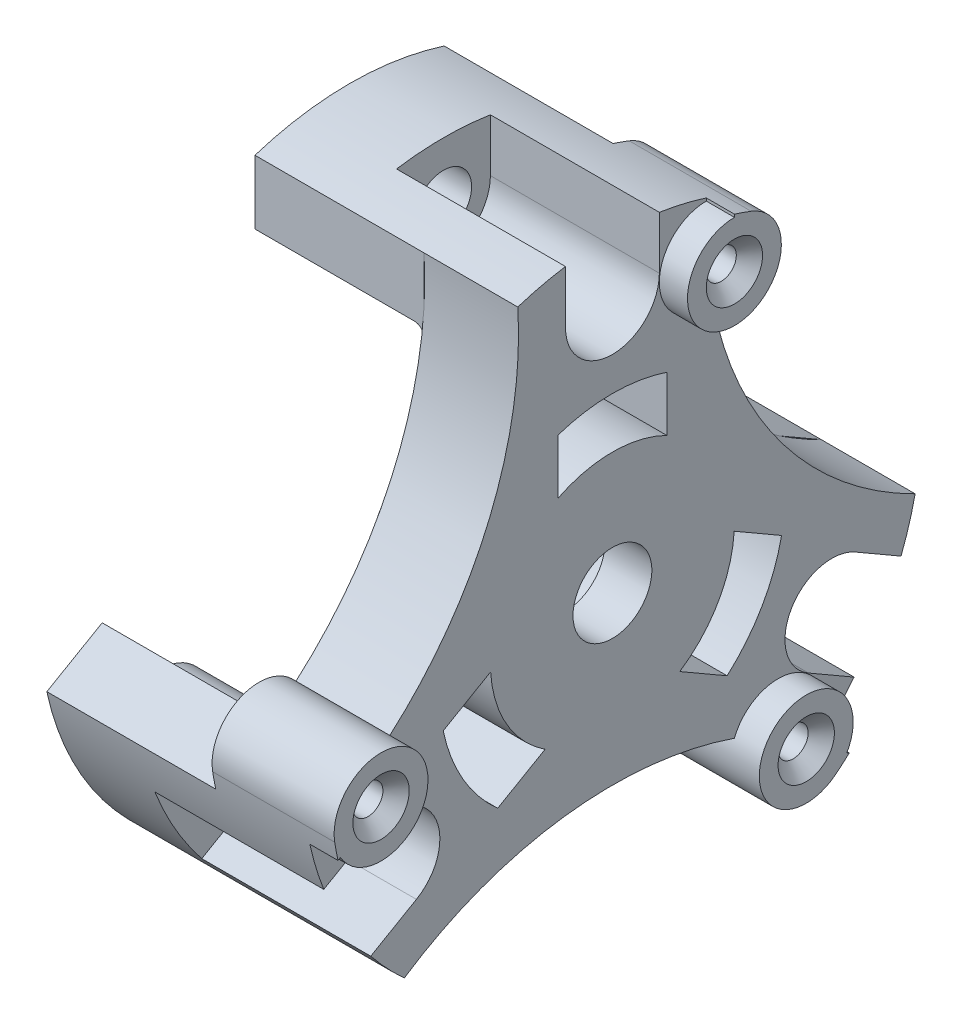
SolidWorks part; units mm, degrees
ref_plane "Front" through (0, 0, 0) normal (0, 0, 1) x (1, 0, 0)
ref_plane "Top" through (0, 0, 0) normal (0, 1, 0) x (1, 0, 0)
ref_plane "Right" through (0, 0, 0) normal (1, 0, 0) x (0, 0, -1)
sketch "草图1" plane through (0, 0, 0) normal (0, 0, 1) x (1, 0, 0)
  line L0 (-65.7429, 0) -> (89.5714, 0) construction
  line L1 (0, 67.1143) -> (0, -71.9143) construction
  line L2 (-7, 6.5) -> (-5, 6.5)
  line L3 (-5, 6.5) -> (-5, 16.5)
  line L4 (-5, 16.5) -> (0, 16.5)
  line L5 (0, 16.5) -> (0, 2.1)
  line L6 (-2.5, 4) -> (-7, 4)
  line L7 (-7, 4) -> (-7, 6.5)
  line L8 (-2.5, 4) -> (-2.5, 2.1)
  line L9 (-2.5, 2.1) -> (0, 2.1)
  dimension "D1" = 4.2
  dimension "D2" = 2.5
  dimension "D3" = 8
  dimension "D4" = 7
  dimension "D5" = 5
  dimension "D6" = 13
  dimension "D7" = 33
revolve "旋转1" add sketch "草图1" angle 360 about L0
sketch "草图2" plane through (-5, 0, 0) normal (-1, 0, 0) x (0, 0, 1)
  line L0 (-23.9515, 0) -> (26.381, 0) construction
  line L1 (0, 44.3891) -> (0, -20.5254) construction
  line L2 (0, 0) -> (-21.2641, -12.2768) construction
  line L3 (0, 0) -> (20.7932, -12.005) construction
  line L4 (0, 0) -> (-61.1055, 35.2793) construction
  line L5 (-5, 31.2128) -> (-5, 9) construction
  line L6 (5, 31.2128) -> (5, 9) construction
  circle A1 centre (-25, 14.4338) radius 20
  point P7 (0, 9)
  point P9 (-7.6795, 4.4338)
  dimension "D6" = 40
  dimension "D1" = 120
  dimension "D2" = 120
  dimension "D3" = 9
  dimension "D5" = 60
  dimension "D7" = 10
extrude "切除-拉伸1" cut sketch "草图2" against normal blind 10 contours A1
pattern_circular "阵列(圆周)1" count 3 over 360 about axis through (0, 0, 0) along (1, 0, 0) of "切除-拉伸1"
sketch "草图3" plane through (-5, 0, 0) normal (-1, 0, 0) x (0, 0, 1)
  line L0 (0, 18) -> (0, -12.9057) construction
  line L1 (-20.442, 0) -> (20.8303, 0) construction
  line L2 (-2.9, 8.731) -> (-2.9, 5.8172)
  line L4 (2.9, 8.731) -> (2.9, 5.8172)
  arc A0 (2.9, 8.731) -> (-2.9, 8.731) centre (0, 0) ccw
  circle A1 centre (0, 0) radius 6.5 construction
  arc A2 (2.9, 5.8172) -> (-2.9, 5.8172) centre (0, 0) ccw
  dimension "D1" = 9.2
  dimension "D2" = 5.8
extrude "切除-拉伸2" cut sketch "草图3" against normal blind 10
pattern_circular "阵列(圆周)2" count 3 over 360 about axis through (0, 0, 0) along (1, 0, 0) of "切除-拉伸2"
sketch "草图4" plane through (-5, 0, 0) normal (-1, 0, 0) x (0, 0, 1)
  line L0 (-16.7535, 0) -> (15.8993, 0) construction
  line L1 (0, 19.3876) -> (0, -16.6742) construction
  line L2 (-5.0408, 15.7111) -> (-5.0408, 12.3077)
  line L4 (5.0408, 12.3077) -> (5.0408, 15.7111)
  circle A0 centre (0, 0) radius 13.5 construction
  arc A1 (5.0408, 15.7111) -> (-5.0408, 15.7111) centre (0, 0) ccw construction
  arc A2 (5.0408, 15.7111) -> (-5.0408, 15.7111) centre (0, 0) ccw
  circle A3 centre (0, 13.5) radius 1.5
  arc A4 (-2.757, 13.0111) -> (2.757, 13.0111) centre (0, 13.5) ccw
  arc A5 (-2.757, 13.0111) -> (-5.0408, 12.3077) centre (0, 0) ccw
  arc A6 (5.0408, 12.3077) -> (2.757, 13.0111) centre (0, 0) ccw
  dimension "D1" = 27
  dimension "D2" = 3
  dimension "D4" = 5.6
  dimension "D5" = 26.6
extrude "凸台-拉伸1" add sketch "草图4" along normal blind 9
pattern_circular "阵列(圆周)3" count 3 over 360 about axis through (0, 0, 0) along (1, 0, 0) of "凸台-拉伸1"
sketch "草图5" plane through (-14, 0, 0) normal (-1, 0, 0) x (0, 0, 1)
  line L0 (-16.1323, 0) -> (16.637, 0) construction
  line L1 (0, 17.8058) -> (0, -12.3621) construction
  line L2 (-3.05, 14) -> (3.05, 14)
  line L3 (-3.05, 14) -> (-3.05, 9.2908)
  line L4 (-3.05, 9.2908) -> (3.05, 9.2908)
  line L5 (3.05, 14) -> (3.05, 9.2908)
  point P10 (0, 9.2908)
  point P11 (0, 14)
  dimension "D1" = 14
  dimension "D2" = 6.1
extrude "切除-拉伸3" cut sketch "草图5" against normal blind 1.5 draft 1 contours L4 L5 L2 L3
sketch "草图10" plane through (-5, 0, 0) normal (-1, 0, 0) x (0, 0, 1)
  point P1 (0, 0)
  dimension "D1" = 12.8775
pattern_circular "阵列(圆周)4" count 3 over 360 about axis through (0, 0, 0) along (1, 0, 0) of "切除-拉伸3"
sketch "草图6" plane through (0, 0, 0) normal (1, 0, 0) x (0, 0, -1)
  line L0 (-17.245, 0) -> (20.4566, 0) construction
  line L1 (0, 20.1005) -> (0, -14.3306) construction
  line L2 (-2.5, 16.3095) -> (-2.5, 13.5)
  line L3 (2.5, 16.3095) -> (2.5, 13.5)
  circle A0 centre (0, 0) radius 13.5 construction
  arc A1 (5.0408, 15.7111) -> (-5.0408, 15.7111) centre (0, 0) ccw construction
  arc A3 (2.5, 16.3095) -> (-2.5, 16.3095) centre (0, 0) ccw
  arc A4 (-2.5, 13.5) -> (2.5, 13.5) centre (0, 13.5) ccw
  dimension "D1" = 27
  dimension "D3" = 5
  dimension "D2" = 5
extrude "切除-拉伸4" cut sketch "草图6" against normal blind 9
pattern_circular "阵列(圆周)5" count 3 over 360 about axis through (0, 0, 0) along (1, 0, 0) of "切除-拉伸4"
sketch "草图7" plane through (-5, 0, 0) normal (-1, 0, 0) x (0, 0, 1)
  line L0 (0, 19.1221) -> (0, -13.8647) construction
  line L1 (16.0973, 0) -> (-17.961, 0) construction
  line L2 (-5, 15.5767) -> (-5, 15.7242)
  arc A1 (-5.8929, 15.4118) -> (-5, 15.5767) centre (-5, 13.0767) ccw
  circle A5 centre (0, 0) radius 14 construction
  arc A6 (-2.5, 16.3095) -> (-5.0408, 15.7111) centre (0, 0) ccw construction
  arc A7 (-5, 15.7242) -> (-5.8929, 15.4118) centre (0, 0) ccw
  point P7 (-5, 13.0767)
  dimension "D1" = 28
  dimension "D3" = 5
  dimension "D2" = 5
extrude "凸台-拉伸2" add sketch "草图7" against normal blind 6.5 contours A1 L2 A7
sketch "草图9" plane through (1.5, 0, 0) normal (1, 0, 0) x (0, 0, -1)
  line L0 (0, 17.5729) -> (0, -10.6538) construction
  line L1 (-14.0745, 0) -> (16.4041, 0) construction
  circle A0 centre (0, 0) radius 14 construction
  circle A1 centre (5, 13.0767) radius 0.8
  dimension "D1" = 1.6
extrude "切除-拉伸7" cut sketch "草图9" against normal blind 6.4 contours A1
chamfer "倒角3" distance 0.7 angle 45 1 edges at (1.5, 13.0767, -5.8)
pattern_circular "阵列(圆周)8" count 3 over 360 about axis through (0, 0, 0) along (1, 0, 0) of "凸台-拉伸2", "切除-拉伸7", "倒角3"
chamfer "倒角4" distance 0.3 angle 45 1 edges at (-7, 0, 4)
fillet "圆角5" radius 0.2 6 edges at (-13.2501, -9.1044, -9.6954) (-13.2501, -3.8443, -12.7323) (-13.2501, 12.9486, -3.0369) (-13.2501, 12.9486, 3.0369) (-13.2501, -3.8443, 12.7323) (-13.2501, -9.1044, 9.6954)
fillet "圆角6" radius 0.5 9 edges at (-5, 12.7108, 3.9147) (-5, 12.7108, -3.9147) (-5, 10.7, 0) (-5, -2.9651, -12.9653) (-5, -5.35, -9.2665) (-5, -9.7457, -9.0505) (-5, -9.7457, 9.0505) (-5, -2.9651, 12.9653) (-5, -5.35, 9.2665)
fillet "圆角7" radius 0.5 1 edges at (-7, 0, 6.5)
